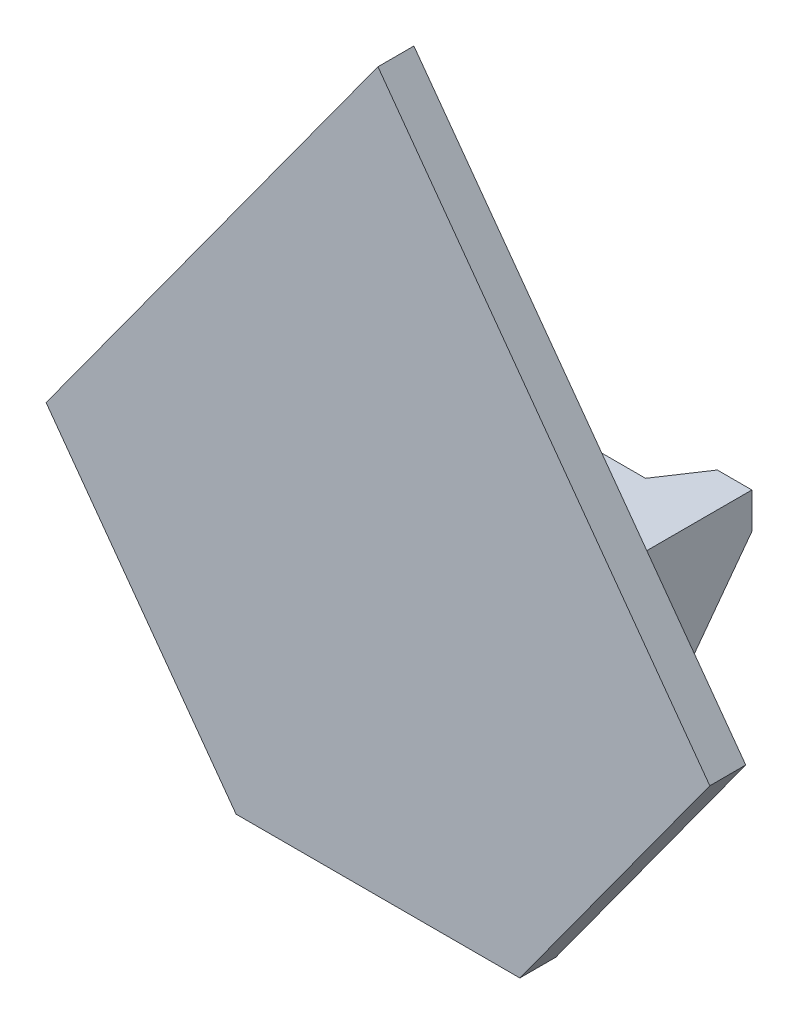
SolidWorks part; units mm, degrees
ref_plane "Front Plane" through (0, 0, 0) normal (0, 0, 1) x (1, 0, 0)
ref_plane "Top Plane" through (0, 0, 0) normal (0, 1, 0) x (1, 0, 0)
ref_plane "Right Plane" through (0, 0, 0) normal (1, 0, 0) x (0, 0, -1)
sketch "Sketch2" plane through (0, 0, 0) normal (0, 1, 0) x (1, 0, 0)
  line L0 (15.061, 0) -> (15.061, 32)
  line L1 (-12.561, 2.5) -> (12.561, 2.5)
  line L2 (-12.561, 2.5) -> (-12.561, 32)
  line L4 (12.561, 2.5) -> (12.561, 32)
  line L5 (15.061, 32) -> (12.561, 32)
  line L7 (-15.061, 32) -> (-15.061, 0)
  line L8 (-15.061, 0) -> (15.061, 0)
  line L10 (-15.061, 32) -> (-12.561, 32)
  point P4 (0, 2.5)
  point P12 (0, 0)
  dimension "D1" = 2.5
  dimension "D2" = 2.5
  dimension "D3" = 29.5
  dimension "D4" = 25.122
extrude "Boss-Extrude1" add sketch "Sketch2" along normal blind 32.5
sketch "Sketch4" plane through (0, 0, 0) normal (0, -1, 0) x (1, 0, 0)
  line L4 (-7.5, -6) -> (7.5, -6)
  line L9 (15.061, 0) -> (-15.061, 0)
  line L13 (-12.561, -2.5) -> (-12.561, -32) construction
  line L18 (-12.561, -10) -> (-7.5, -6)
  line L23 (12.561, -32) -> (12.561, -2.5) construction
  line L26 (12.561, -10) -> (7.5, -6)
  line L32 (-12.561, -10) -> (-15.061, -10)
  line L33 (-15.061, -32) -> (-15.061, 0) construction
  line L34 (-15.061, -10) -> (-15.061, 0)
  line L35 (12.561, -10) -> (15.061, -10)
  line L36 (15.061, 0) -> (15.061, -32) construction
  line L37 (15.061, -10) -> (15.061, 0)
  circle A2 centre (-10.2499, -4.95) radius 1.05
  circle A5 centre (10.2499, -4.95) radius 1.05
  point P31 (0, -6)
  dimension "D5" = 2.1
  dimension "D10" = 15
  dimension "D11" = 10
  dimension "D2" = 6
  dimension "D7" = 4.95
extrude "Boss-Extrude2" add sketch "Sketch4" along normal blind 1.5
sketch "Sketch5" plane through (0, 32.5, 0) normal (0, 1, 0) x (1, 0, 0)
  line L0 (-15.061, 32) -> (-10.2499, 32)
  line L9 (-10.2499, 32) -> (-6.25, 26)
  line L13 (-15.061, 0) -> (15.061, 0) construction
  line L14 (15.061, 0) -> (-15.061, 0)
  line L15 (-15.061, 0) -> (-15.061, 32)
  line L20 (15.061, 0) -> (15.061, 32)
  line L21 (-6.25, 26) -> (6.25, 26)
  line L22 (6.25, 26) -> (10.2499, 32)
  line L23 (10.2499, 32) -> (15.061, 32)
  circle A0 centre (-10.2499, 4.95) radius 1.05 construction
  circle A1 centre (-10.2499, 8.7) radius 1.05
  circle A2 centre (10.2499, 8.7) radius 1.05
  point P6 (0, 26)
  dimension "D4" = 0
  dimension "D1" = 8.7
  dimension "D2" = 12.5
  dimension "D3" = 20.4998
  dimension "D5" = 6
extrude "Boss-Extrude3" add sketch "Sketch5" along normal blind 2
sketch "Sketch6" plane through (-15.061, 0, 0) normal (-1, 0, 0) x (0, 0, 1)
  line L0 (-10, 0) -> (-32, 29.5)
  line L1 (-32, 29.5) -> (-32, 0)
  line L2 (-32, 0) -> (-10, 0)
  line L3 (-32, 34.5) -> (-32, 0) construction
  dimension "D1" = 5
extrude "Cut-Extrude1" cut sketch "Sketch6" against normal through all
ref_plane "Plane1" through (0, 16.5, 0) normal (0, -1, 0) x (-1, 0, 0)
sketch "Sketch8" plane through (0, 0, 0) normal (0, 0, 1) x (1, 0, 0)
  line L0 (0, 96.5) -> (58.1234, 16.5)
  line L1 (-16.5671, 16.5) -> (16.5671, 16.5) construction
  line L2 (58.1234, 16.5) -> (-58.1234, 16.5)
  line L3 (-58.1234, 16.5) -> (0, 96.5)
  point P4 (0, 0)
  point P6 (42.664, 16.5)
  point P8 (0, 60.0116)
  dimension "D1" = 72
  dimension "D2" = 80
extrude "Boss-Extrude4" add sketch "Sketch8" along normal blind 5
sketch "Sketch9" plane through (0, 0, 0) normal (0, 0, 1) x (1, 0, 0)
  line L0 (-58.1234, 16.5) -> (-72.6543, -3.5)
  line L1 (-72.6543, -3.5) -> (72.6543, -3.5)
  line L2 (72.6543, -3.5) -> (58.1234, 16.5)
  line L3 (-58.1234, 16.5) -> (58.1234, 16.5)
  line L4 (0, 96.5) -> (-58.1234, 16.5) construction
  line L5 (58.1234, 16.5) -> (0, 96.5) construction
  dimension "D1" = 20
extrude "Boss-Extrude6" add sketch "Sketch9" along normal up to surface (5 mm away) up to face at (0, 43.1667, 5)
sketch "Sketch10" plane through (0, 0, 0) normal (0, 0, -1) x (-1, 0, 0)
  line L0 (-19.7536, -3.5) -> (-46.2039, 32.9058)
  line L1 (72.6543, -3.5) -> (-72.6543, -3.5) construction
  line L2 (-72.6543, -3.5) -> (0, 96.5) construction
  line L3 (-46.2039, 32.9058) -> (-72.6543, -3.5)
  line L4 (-72.6543, -3.5) -> (-19.7536, -3.5)
  line L5 (72.6543, -3.5) -> (46.2039, 32.9058)
  line L13 (0, 96.5) -> (72.6543, -3.5) construction
  line L14 (46.2039, 32.9058) -> (19.7536, -3.5)
  line L15 (72.6543, -3.5) -> (-72.6543, -3.5) construction
  line L16 (19.7536, -3.5) -> (72.6543, -3.5)
  point P10 (0, 0)
  point P13 (46.2039, -3.5)
  dimension "D1" = 45
extrude "Cut-Extrude2" cut sketch "Sketch10" against normal through all
